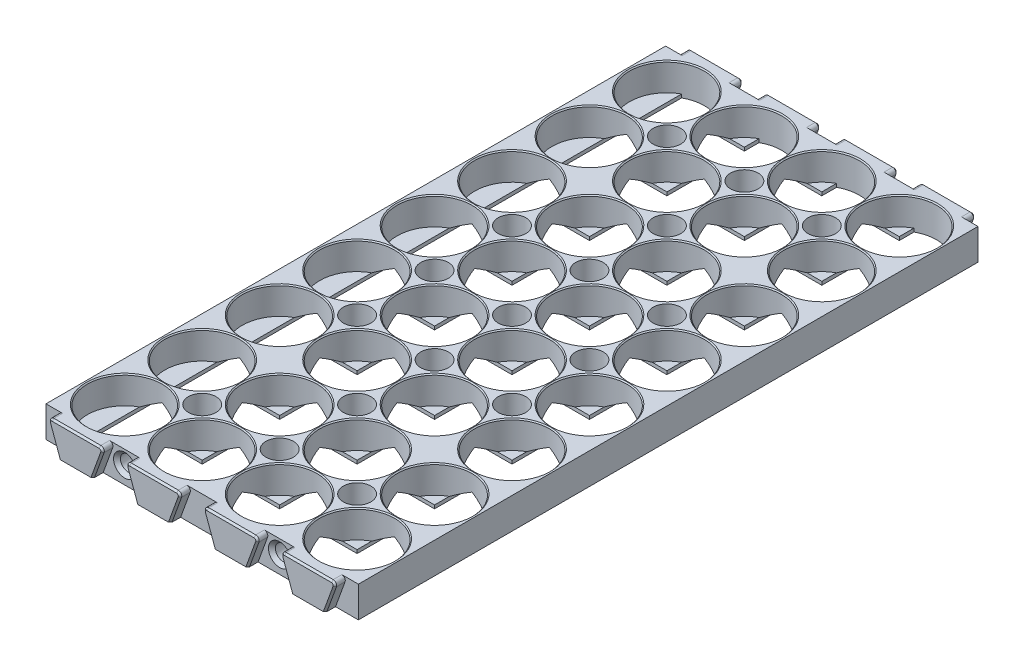
SolidWorks part; units mm, degrees
ref_plane "Front Plane" through (0, 0, 0) normal (0, 0, 1) x (1, 0, 0)
ref_plane "Top Plane" through (0, 0, 0) normal (0, 1, 0) x (1, 0, 0)
ref_plane "Right Plane" through (0, 0, 0) normal (1, 0, 0) x (0, 0, -1)
sketch "Sketch1" plane through (0, 0, 0) normal (0, 1, 0) x (1, 0, 0)
  line L0 (-11.25, 10.875) -> (11.25, 10.875) construction
  line L1 (-11.25, -11.25) -> (11.25, -11.25)
  line L2 (-11.25, -11.25) -> (-11.25, 11.25)
  line L3 (-11.25, 11.25) -> (11.25, 11.25)
  line L4 (11.25, -11.25) -> (11.25, 11.25)
  line L5 (-11.25, -11.25) -> (11.25, 11.25) construction
  line L6 (-11.25, 11.25) -> (11.25, -11.25) construction
  circle A0 centre (0, 0) radius 10.875
  point P0 (0, 0)
  dimension "D1" = 21.75
  dimension "D2" = 22.5
  dimension "D3" = 0.375
extrude "Boss-Extrude1" add sketch "Sketch1" along normal blind 8
sketch "Sketch2" plane through (0, 0, 0) normal (0, -1, 0) x (1, 0, 0)
  line L0 (5.25, 11.25) -> (-5.25, 11.25) construction
  line L1 (11.25, 11.25) -> (5.25, 11.25)
  line L2 (11.25, 11.25) -> (11.25, 5.25)
  line L3 (11.25, 5.25) -> (5.25, 5.25)
  line L4 (5.25, 11.25) -> (5.25, 5.25)
  line L5 (11.25, -11.25) -> (5.25, -11.25)
  line L6 (11.25, -11.25) -> (11.25, -5.25)
  line L7 (11.25, -5.25) -> (5.25, -5.25)
  line L8 (5.25, -11.25) -> (5.25, -5.25)
  line L9 (-11.25, -11.25) -> (-5.25, -11.25)
  line L10 (-11.25, -11.25) -> (-11.25, -5.25)
  line L11 (-11.25, -5.25) -> (-5.25, -5.25)
  line L12 (-5.25, -11.25) -> (-5.25, -5.25)
  line L13 (-11.25, 11.25) -> (-5.25, 11.25)
  line L14 (-11.25, 11.25) -> (-11.25, 5.25)
  line L15 (-11.25, 5.25) -> (-5.25, 5.25)
  line L16 (-5.25, 11.25) -> (-5.25, 5.25)
  line L17 (11.25, 5.25) -> (11.25, -5.25) construction
  line L18 (5.25, -11.25) -> (-5.25, -11.25) construction
  line L19 (-11.25, 5.25) -> (-11.25, -5.25) construction
  dimension "D1" = 10.5
extrude "Boss-Extrude2" add sketch "Sketch2" along normal blind 1
chamfer "Chamfer2" distance 0.3 angle 45 1 edges at (0, 8, 10.875)
pattern_linear "LPattern1" count 8 spacing 22.5 along (0, 0, 1) count 4 spacing 22.5 along (1, 0, 0) of "Boss-Extrude2", "Boss-Extrude1", "Chamfer2"
sketch "Sketch5" plane through (0, 0, -5.25) normal (0, 0, 1) x (1, 0, 0)
  line L0 (72.75, -1) -> (72.75, 0) construction
  line L20 (78.75, -1) -> (72.75, -1) construction
  line L25 (-5.25, -1) -> (-5.25, 0) construction
  line L26 (-5.25, -1) -> (-11.25, -1) construction
  line L27 (-11.25, -1) -> (-11.25, 0) construction
  line L29 (-5.25, 0) -> (-9.5238, 0) construction
  line L35 (-5.25, -1) -> (-5.25, 0)
  line L36 (-5.25, -1) -> (-11.25, -1)
  line L37 (-11.25, -1) -> (-11.25, 0)
  line L39 (-5.25, 0) -> (-11.25, 0)
  line L46 (78.75, -1) -> (78.75, 0) construction
  line L47 (78.75, 0) -> (77.0238, 0) construction
  line L48 (77.0238, 0) -> (72.75, 0) construction
  line L49 (72.75, -1) -> (72.75, 0)
  line L50 (78.75, -1) -> (72.75, -1)
  line L51 (78.75, -1) -> (78.75, 0)
  line L52 (78.75, 0) -> (77.0238, 0)
  line L53 (77.0238, 0) -> (72.75, 0)
  dimension "D1" = 6
extrude "Boss-Extrude3" add sketch "Sketch5" along normal up to surface (174 mm away)
sketch "Sketch6" plane through (0, 0, 0) normal (0, -1, 0) x (1, 0, 0)
  line L24 (62.25, -11.25) -> (72.75, -11.25) construction
  line L25 (72.75, -11.25) -> (72.75, -9.5238) construction
  line L26 (62.25, -9.5238) -> (62.25, -11.25) construction
  line L27 (39.75, -11.25) -> (50.25, -11.25) construction
  line L28 (50.25, -11.25) -> (50.25, -9.5238) construction
  line L29 (39.75, -9.5238) -> (39.75, -11.25) construction
  line L30 (17.25, -9.5238) -> (17.25, -11.25) construction
  line L31 (17.25, -11.25) -> (27.75, -11.25) construction
  line L32 (27.75, -11.25) -> (27.75, -9.5238) construction
  line L33 (-5.25, -9.5238) -> (-5.25, -11.25) construction
  line L34 (-5.25, -11.25) -> (5.25, -11.25) construction
  line L35 (5.25, -11.25) -> (5.25, -9.5238) construction
  line L48 (62.25, -11.25) -> (72.75, -11.25)
  line L49 (72.75, -11.25) -> (72.75, -9.5238)
  line L50 (62.25, -9.5238) -> (62.25, -11.25)
  line L51 (39.75, -11.25) -> (50.25, -11.25)
  line L52 (50.25, -11.25) -> (50.25, -9.5238)
  line L53 (39.75, -9.5238) -> (39.75, -11.25)
  line L54 (17.25, -9.5238) -> (17.25, -11.25)
  line L55 (17.25, -11.25) -> (27.75, -11.25)
  line L56 (27.75, -11.25) -> (27.75, -9.5238)
  line L57 (-5.25, -9.5238) -> (-5.25, -11.25)
  line L58 (-5.25, -11.25) -> (5.25, -11.25)
  line L59 (5.25, -11.25) -> (5.25, -9.5238)
  line L84 (5.25, 168.75) -> (-5.25, 168.75) construction
  line L85 (-5.25, 168.75) -> (-5.25, 167.0238) construction
  line L86 (5.25, 167.0238) -> (5.25, 168.75) construction
  line L87 (27.75, 167.0238) -> (27.75, 168.75) construction
  line L88 (27.75, 168.75) -> (17.25, 168.75) construction
  line L89 (17.25, 168.75) -> (17.25, 167.0238) construction
  line L90 (72.75, 167.0238) -> (72.75, 168.75) construction
  line L91 (72.75, 168.75) -> (62.25, 168.75) construction
  line L92 (62.25, 168.75) -> (62.25, 167.0238) construction
  line L93 (50.25, 167.0238) -> (50.25, 168.75) construction
  line L94 (50.25, 168.75) -> (39.75, 168.75) construction
  line L95 (39.75, 168.75) -> (39.75, 167.0238) construction
  line L96 (5.25, 168.75) -> (-5.25, 168.75)
  line L97 (-5.25, 168.75) -> (-5.25, 167.0238)
  line L98 (5.25, 167.0238) -> (5.25, 168.75)
  line L99 (27.75, 167.0238) -> (27.75, 168.75)
  line L100 (27.75, 168.75) -> (17.25, 168.75)
  line L101 (17.25, 168.75) -> (17.25, 167.0238)
  line L102 (72.75, 167.0238) -> (72.75, 168.75)
  line L103 (72.75, 168.75) -> (62.25, 168.75)
  line L104 (62.25, 168.75) -> (62.25, 167.0238)
  line L105 (50.25, 167.0238) -> (50.25, 168.75)
  line L106 (50.25, 168.75) -> (39.75, 168.75)
  line L107 (39.75, 168.75) -> (39.75, 167.0238)
  arc A8 (62.25, -9.5238) -> (72.75, -9.5238) centre (67.5, 0) ccw construction
  arc A9 (39.75, -9.5238) -> (50.25, -9.5238) centre (45, 0) ccw construction
  arc A10 (17.25, -9.5238) -> (27.75, -9.5238) centre (22.5, 0) ccw construction
  arc A11 (-5.25, -9.5238) -> (5.25, -9.5238) centre (0, 0) ccw construction
  arc A16 (62.25, -9.5238) -> (72.75, -9.5238) centre (67.5, 0) ccw
  arc A17 (39.75, -9.5238) -> (50.25, -9.5238) centre (45, 0) ccw
  arc A18 (17.25, -9.5238) -> (27.75, -9.5238) centre (22.5, 0) ccw
  arc A19 (-5.25, -9.5238) -> (5.25, -9.5238) centre (0, 0) ccw
  arc A28 (5.25, 167.0238) -> (-5.25, 167.0238) centre (0, 157.5) ccw construction
  arc A29 (27.75, 167.0238) -> (17.25, 167.0238) centre (22.5, 157.5) ccw construction
  arc A30 (72.75, 167.0238) -> (62.25, 167.0238) centre (67.5, 157.5) ccw construction
  arc A31 (50.25, 167.0238) -> (39.75, 167.0238) centre (45, 157.5) ccw construction
  arc A32 (5.25, 167.0238) -> (-5.25, 167.0238) centre (0, 157.5) ccw
  arc A33 (27.75, 167.0238) -> (17.25, 167.0238) centre (22.5, 157.5) ccw
  arc A34 (72.75, 167.0238) -> (62.25, 167.0238) centre (67.5, 157.5) ccw
  arc A35 (50.25, 167.0238) -> (39.75, 167.0238) centre (45, 157.5) ccw
extrude "Boss-Extrude4" add sketch "Sketch6" along normal up to surface (1 mm away) up to face at (-8.25, -1, 78.75)
sketch "Sketch7" plane through (0, 0, 0) normal (0, 0, 1) x (1, 0, 0)
  line L0 (-11.25, 8) -> (78.75, 8) construction
  line L1 (-5.25, 0) -> (5.25, 0)
  line L2 (-5.25, 0) -> (0, 5.25) construction
  line L3 (0, 5.25) -> (5.25, 0) construction
  line L4 (0, 0) -> (0, 8) construction
  line L6 (-5.25, 0) -> (0, 3.0311)
  line L7 (0, 3.0311) -> (5.25, 0)
  line L9 (-5.25, -1) -> (-5.25, 0) construction
  line L10 (5.25, -1) -> (5.25, 0) construction
  line L11 (-5.25, -1) -> (-5.25, 0) construction
  line L12 (5.25, -1) -> (5.25, 0) construction
  line L13 (17.25, 0) -> (22.5, 3.0311)
  line L14 (22.5, 3.0311) -> (27.75, 0)
  line L15 (17.25, 0) -> (27.75, 0)
  line L16 (39.75, 0) -> (45, 3.0311)
  line L17 (45, 3.0311) -> (50.25, 0)
  line L18 (39.75, 0) -> (50.25, 0)
  line L19 (62.25, 0) -> (67.5, 3.0311)
  line L20 (67.5, 3.0311) -> (72.75, 0)
  line L21 (62.25, 0) -> (72.75, 0)
  line L22 (-5.25, 0) -> (17.25, 0) construction
  dimension "D1" = 45
  dimension "D2" = 30
  dimension "D3" = 4.9689
  dimension "D5" = 22.5
  dimension "D4" = 4
extrude "Cut-Extrude1" cut sketch "Sketch7" along normal up to surface (162.75 mm away) up to face at (56.25, -0.3333, 162.75)
sketch "Sketch16" plane through (0, 0, 0) normal (1, 0, 0) x (0, 0, -1)
  line L2 (-5.25, -1) -> (-5.25, 0) construction
  line L3 (5.25, -1) -> (5.25, 0) construction
  line L4 (-5.25, 0) -> (0, 3.0311)
  line L5 (0, 3.0311) -> (5.25, 0)
  line L6 (-5.25, 0) -> (5.25, 0)
  line L7 (-5.25, -1) -> (-5.25, 0) construction
  line L8 (5.25, -1) -> (5.25, 0) construction
  line L9 (-22.5, 3.0311) -> (-17.25, 0)
  line L10 (-27.75, 0) -> (-17.25, 0)
  line L11 (-27.75, 0) -> (-22.5, 3.0311)
  line L12 (-45, 3.0311) -> (-39.75, 0)
  line L13 (-50.25, 0) -> (-39.75, 0)
  line L14 (-50.25, 0) -> (-45, 3.0311)
  line L15 (-67.5, 3.0311) -> (-62.25, 0)
  line L16 (-72.75, 0) -> (-62.25, 0)
  line L17 (-72.75, 0) -> (-67.5, 3.0311)
  line L18 (-90, 3.0311) -> (-84.75, 0)
  line L19 (-95.25, 0) -> (-84.75, 0)
  line L20 (-95.25, 0) -> (-90, 3.0311)
  line L21 (-112.5, 3.0311) -> (-107.25, 0)
  line L22 (-117.75, 0) -> (-107.25, 0)
  line L23 (-117.75, 0) -> (-112.5, 3.0311)
  line L24 (-135, 3.0311) -> (-129.75, 0)
  line L25 (-140.25, 0) -> (-129.75, 0)
  line L26 (-140.25, 0) -> (-135, 3.0311)
  line L27 (-157.5, 3.0311) -> (-152.25, 0)
  line L28 (-162.75, 0) -> (-152.25, 0)
  line L29 (-162.75, 0) -> (-157.5, 3.0311)
  line L30 (-180, 3.0311) -> (-174.75, 0)
  line L31 (-185.25, 0) -> (-174.75, 0)
  line L32 (-185.25, 0) -> (-180, 3.0311)
  line L33 (-202.5, 3.0311) -> (-197.25, 0)
  line L34 (-207.75, 0) -> (-197.25, 0)
  line L35 (-207.75, 0) -> (-202.5, 3.0311)
  line L36 (-225, 3.0311) -> (-219.75, 0)
  line L37 (-230.25, 0) -> (-219.75, 0)
  line L38 (-230.25, 0) -> (-225, 3.0311)
  line L39 (-247.5, 3.0311) -> (-242.25, 0)
  line L40 (-252.75, 0) -> (-242.25, 0)
  line L41 (-252.75, 0) -> (-247.5, 3.0311)
  line L42 (0, 3.0311) -> (-22.5, 3.0311) construction
  dimension "D1" = 30
  dimension "D3" = 22.5
  dimension "D2" = 12
extrude "Cut-Extrude7" cut sketch "Sketch16" along normal up to surface (62.25 mm away) up to face at (62.25, -0.3333, 11.25)
sketch "Sketch8" plane through (0, 0, -11.25) normal (0, 0, -1) x (-1, 0, 0)
  line L0 (0, -1) -> (0, 8) construction
  line L1 (-27.4743, -1) -> (-30.75, 8)
  line L2 (-78.75, 8) -> (11.25, 8) construction
  line L3 (4.9743, -1) -> (-4.9743, -1)
  line L4 (-4.9743, -1) -> (-8.25, 8)
  line L5 (-8.25, 8) -> (8.25, 8)
  line L6 (4.9743, -1) -> (8.25, 8)
  line L7 (11.25, 8) -> (11.25, -1) construction
  line L8 (11.25, -1) -> (-78.75, -1) construction
  line L9 (-30.75, 8) -> (-14.25, 8)
  line L10 (-78.75, 8) -> (11.25, 8) construction
  line L11 (-17.5257, -1) -> (-14.25, 8)
  line L12 (-17.5257, -1) -> (-27.4743, -1)
  line L13 (-49.9743, -1) -> (-53.25, 8)
  line L14 (-53.25, 8) -> (-36.75, 8)
  line L15 (-40.0257, -1) -> (-36.75, 8)
  line L16 (-40.0257, -1) -> (-49.9743, -1)
  line L17 (-72.4743, -1) -> (-75.75, 8)
  line L18 (-75.75, 8) -> (-59.25, 8)
  line L19 (-62.5257, -1) -> (-59.25, 8)
  line L20 (-62.5257, -1) -> (-72.4743, -1)
  line L21 (-4.9743, -1) -> (-27.4743, -1) construction
  line L22 (-78.75, 8) -> (11.25, 8) construction
  dimension "D1" = 70
  dimension "D2" = 3
  dimension "D4" = 22.5
  dimension "D5" = 9
  dimension "D3" = 4
sketch "Sketch9" plane through (0, 0, 168.75) normal (0, 0, 1) x (1, 0, 0)
  line L24 (-4.9743, -1) -> (4.9743, -1)
  line L25 (4.9743, -1) -> (8.25, 8)
  line L26 (8.25, 8) -> (-8.25, 8)
  line L27 (-8.25, 8) -> (-4.9743, -1)
  line L28 (-4.9743, -1) -> (4.9743, -1)
  line L29 (4.9743, -1) -> (8.25, 8)
  line L30 (8.25, 8) -> (-8.25, 8)
  line L31 (-8.25, 8) -> (-4.9743, -1)
  line L32 (72.4743, -1) -> (75.75, 8)
  line L33 (75.75, 8) -> (59.25, 8)
  line L34 (59.25, 8) -> (62.5257, -1)
  line L35 (62.5257, -1) -> (72.4743, -1)
  line L36 (72.4743, -1) -> (75.75, 8)
  line L37 (75.75, 8) -> (59.25, 8)
  line L38 (59.25, 8) -> (62.5257, -1)
  line L39 (62.5257, -1) -> (72.4743, -1)
  line L40 (49.9743, -1) -> (53.25, 8)
  line L41 (53.25, 8) -> (36.75, 8)
  line L42 (36.75, 8) -> (40.0257, -1)
  line L43 (40.0257, -1) -> (49.9743, -1)
  line L44 (49.9743, -1) -> (53.25, 8)
  line L45 (53.25, 8) -> (36.75, 8)
  line L46 (36.75, 8) -> (40.0257, -1)
  line L47 (40.0257, -1) -> (49.9743, -1)
  line L48 (14.25, 8) -> (17.5257, -1)
  line L49 (17.5257, -1) -> (27.4743, -1)
  line L50 (27.4743, -1) -> (30.75, 8)
  line L51 (30.75, 8) -> (14.25, 8)
  line L52 (14.25, 8) -> (17.5257, -1)
  line L53 (17.5257, -1) -> (27.4743, -1)
  line L54 (27.4743, -1) -> (30.75, 8)
  line L55 (30.75, 8) -> (14.25, 8)
  dimension "D1" = 0
  dimension "D2" = 0
  dimension "D3" = 0
  dimension "D4" = 0
extrude "Boss-Extrude5" add sketch "Sketch8" along normal blind 3
extrude "Boss-Extrude6" add sketch "Sketch9" along normal blind 3
fillet "Fillet1" radius 1 16 edges at (14.25, 8, -12.75) (8.25, 8, -12.75) (-8.25, 8, -12.75) (30.75, 8, -12.75) (59.25, 8, -12.75) (53.25, 8, -12.75) (36.75, 8, -12.75) (75.75, 8, -12.75) (-8.25, 8, 170.25) (8.25, 8, 170.25) (14.25, 8, 170.25) (30.75, 8, 170.25) (36.75, 8, 170.25) (53.25, 8, 170.25) (59.25, 8, 170.25) (75.75, 8, 170.25)
chamfer "Chamfer3" distance 0.5 angle 45 40 edges at (6.3679, 2.829, -14.25) (0, 8, -14.25) (-6.3679, 2.829, -14.25) (73.8679, 2.829, -14.25) (67.5, 8, -14.25) (61.1321, 2.829, -14.25) (51.3679, 2.829, -14.25) (45, 8, -14.25) (38.6321, 2.829, -14.25) (28.8679, 2.829, -14.25) (22.5, 8, -14.25) (16.1321, 2.829, -14.25) (73.8679, 2.829, 171.75) (61.1321, 2.829, 171.75) (67.5, 8, 171.75) (51.3679, 2.829, 171.75) (38.6321, 2.829, 171.75) (45, 8, 171.75) (28.8679, 2.829, 171.75) (16.1321, 2.829, 171.75) (22.5, 8, 171.75) (6.3679, 2.829, 171.75) (-6.3679, 2.829, 171.75) (0, 8, 171.75) (75.141, 7.5736, 171.75) (59.859, 7.5736, 171.75) (52.641, 7.5736, 171.75) (37.359, 7.5736, 171.75) (30.141, 7.5736, 171.75) (14.859, 7.5736, 171.75) (7.641, 7.5736, 171.75) (-7.641, 7.5736, 171.75) (75.141, 7.5736, -14.25) (59.859, 7.5736, -14.25) (52.641, 7.5736, -14.25) (37.359, 7.5736, -14.25) (30.141, 7.5736, -14.25) (14.859, 7.5736, -14.25) (7.641, 7.5736, -14.25) (-7.641, 7.5736, -14.25)
sketch "Sketch10" plane through (0, 0, -11.25) normal (0, 0, -1) x (-1, 0, 0)
  line L0 (-11.25, -1) -> (-11.25, 8) construction
  line L2 (-4.9743, -1) -> (-17.5257, -1) construction
  line L4 (-14.25, 8) -> (-8.25, 8) construction
  line L5 (-33.75, 8) -> (-33.75, -1) construction
  line L6 (-36.75, 8) -> (-30.75, 8) construction
  line L7 (-27.4743, -1) -> (-40.0257, -1) construction
  circle A0 centre (-11.25, 4) radius 2.25
  circle A1 centre (-56.25, 4) radius 2.25
  dimension "D2" = 4.5
  dimension "D1" = 4
sketch "Sketch11" plane through (0, 0, 168.75) normal (0, 0, 1) x (1, 0, 0)
  circle A0 centre (11.25, 4) radius 2.25 construction
  circle A1 centre (11.25, 4) radius 2.25
  circle A2 centre (56.25, 4) radius 2.25 construction
  circle A3 centre (56.25, 4) radius 2.25
extrude "Cut-Extrude2" cut sketch "Sketch10" against normal blind 5
extrude "Cut-Extrude3" cut sketch "Sketch11" against normal blind 5
chamfer "Chamfer5" distance 1 angle 45 4 edges at (58.5, 4, -11.25) (9, 4, -11.25) (13.5, 4, 168.75) (58.5, 4, 168.75)
sketch "Sketch17" plane through (0, -1, 0) normal (0, -1, 0) x (1, 0, 0)
  line L0 (5.25, 5.25) -> (17.25, 17.25) construction
  line L1 (11.25, 11.25) -> (33.75, 11.25) construction
  circle A0 centre (11.25, 11.25) radius 4
  circle A1 centre (33.75, 11.25) radius 4
  circle A2 centre (56.25, 11.25) radius 4
  circle A33 centre (33.75, 146.25) radius 4 [skipped]
  circle A34 centre (56.25, 146.25) radius 4 [skipped]
  circle A35 centre (33.75, 168.75) radius 4 [skipped]
  circle A36 centre (33.75, 191.25) radius 4 [skipped]
  circle A37 centre (56.25, 191.25) radius 4 [skipped]
  circle A38 centre (33.75, 213.75) radius 4 [skipped]
  circle A39 centre (56.25, 213.75) radius 4 [skipped]
  circle A40 centre (33.75, 236.25) radius 4 [skipped]
  circle A41 centre (56.25, 236.25) radius 4 [skipped]
  circle A42 centre (11.25, 146.25) radius 4 [skipped]
  circle A43 centre (11.25, 191.25) radius 4 [skipped]
  circle A44 centre (11.25, 213.75) radius 4 [skipped]
  circle A45 centre (11.25, 236.25) radius 4 [skipped]
  circle A46 centre (56.25, 168.75) radius 4 construction
  circle A47 centre (11.25, 168.75) radius 4 construction
  circle A48 centre (33.75, 123.75) radius 4 [skipped]
  circle A49 centre (56.25, 123.75) radius 4 [skipped]
  circle A50 centre (11.25, 123.75) radius 4 [skipped]
  circle A51 centre (11.25, 258.75) radius 4
  circle A52 centre (33.75, 258.75) radius 4
  circle A53 centre (56.25, 258.75) radius 4
  circle A54 centre (11.25, 281.25) radius 4
  circle A55 centre (33.75, 281.25) radius 4
  circle A56 centre (56.25, 281.25) radius 4
  circle A57 centre (33.75, 33.75) radius 4 [skipped]
  circle A58 centre (33.75, 56.25) radius 4 [skipped]
  circle A59 centre (56.25, 56.25) radius 4 [skipped]
  circle A60 centre (33.75, 78.75) radius 4 [skipped]
  circle A61 centre (56.25, 78.75) radius 4 [skipped]
  circle A62 centre (33.75, 101.25) radius 4 [skipped]
  circle A63 centre (56.25, 101.25) radius 4 [skipped]
  circle A64 centre (11.25, 56.25) radius 4 [skipped]
  circle A65 centre (11.25, 78.75) radius 4 [skipped]
  circle A66 centre (11.25, 101.25) radius 4 [skipped]
  circle A67 centre (56.25, 33.75) radius 4 construction
  circle A68 centre (11.25, 33.75) radius 4 construction
  circle A69 centre (11.25, 33.75) radius 4 construction
  circle A70 centre (33.75, 33.75) radius 4
  circle A71 centre (56.25, 33.75) radius 4 construction
  circle A72 centre (11.25, 56.25) radius 4
  circle A73 centre (33.75, 56.25) radius 4
  circle A74 centre (56.25, 56.25) radius 4
  circle A75 centre (11.25, 78.75) radius 4
  circle A76 centre (33.75, 78.75) radius 4
  circle A77 centre (56.25, 78.75) radius 4
  circle A78 centre (11.25, 101.25) radius 4
  circle A79 centre (33.75, 101.25) radius 4
  circle A80 centre (56.25, 101.25) radius 4
  circle A81 centre (11.25, 123.75) radius 4 construction
  circle A82 centre (33.75, 123.75) radius 4
  circle A83 centre (56.25, 123.75) radius 4 construction
  circle A84 centre (11.25, 146.25) radius 4
  circle A85 centre (33.75, 146.25) radius 4
  circle A86 centre (56.25, 146.25) radius 4
  dimension "D4" = 22.5
  dimension "D1" = 8
  dimension "D3" = 13
  dimension "D5" = 7
extrude "Cut-Extrude8" cut sketch "Sketch17" against normal through all
sketch "Sketch18" plane through (0, -1, 0) normal (0, -1, 0) x (1, 0, 0)
  line L0 (50.25, 117.75) -> (62.25, 117.75) construction
  line L1 (50.25, 129.75) -> (50.25, 117.75) construction
  line L2 (5.25, 117.75) -> (17.25, 129.75) construction
  line L3 (5.25, 27.75) -> (17.25, 39.75) construction
  line L4 (50.25, 27.75) -> (62.25, 39.75) construction
  line L38 (78.75, 78.75) -> (-11.25, 78.75) construction
  line L39 (78.75, -11.25) -> (78.75, 168.75) construction
  line L40 (-11.25, 168.75) -> (-11.25, -11.25) construction
  line L42 (50.25, 117.75) -> (62.25, 129.75) construction
  circle A0 centre (11.25, 33.75) radius 2.1
  circle A4 centre (56.25, 33.75) radius 2.1
  circle A7 centre (56.25, 123.75) radius 2.1
  circle A8 centre (11.25, 123.75) radius 2.1
  dimension "D1" = 4.2
extrude "Cut-Extrude9" cut sketch "Sketch18" against normal blind 4
sketch "Sketch19" plane through (0, -1, 0) normal (0, -1, 0) x (1, 0, 0)
  line L0 (78.75, 78.75) -> (-11.25, 78.75) construction
  line L1 (78.75, -11.25) -> (78.75, 168.75) construction
  line L2 (-11.25, 168.75) -> (-11.25, -11.25) construction
  circle A2 centre (56.25, 123.75) radius 1.7
  circle A3 centre (11.25, 33.75) radius 1.7
  circle A4 centre (11.25, 123.75) radius 1.7
  circle A5 centre (56.25, 33.75) radius 1.7
  dimension "D1" = 3.4
extrude "Cut-Extrude10" cut sketch "Sketch19" against normal offset from surface (7 mm away) 2 up to face at (11.25, 8, 97.25)
chamfer "Chamfer6" distance 1 angle 45 4 edges at (11.25, -1, 121.65) (56.25, -1, 121.65) (56.25, -1, 31.65) (11.25, -1, 31.65)
sketch "Sketch22" plane through (0, 8, 0) normal (0, 1, 0) x (1, 0, 0)
  line L0 (-11.25, -168.75) -> (-6.8219, -168.75) construction
  line L1 (-11.25, 11.25) -> (-11.625, 11.25)
  line L2 (-11.25, 11.25) -> (-11.25, -168.75)
  line L3 (-11.25, -168.75) -> (-11.625, -168.75)
  line L4 (-11.625, 11.25) -> (-11.625, -168.75)
  line L5 (33.75, 11.25) -> (33.75, -168.75) construction
  line L6 (36.75, 11.25) -> (30.75, 11.25) construction
  line L7 (30.75, -168.75) -> (36.75, -168.75) construction
  line L14 (79.125, 11.25) -> (79.125, -168.75)
  line L15 (78.75, -168.75) -> (79.125, -168.75)
  line L16 (78.75, 11.25) -> (78.75, -168.75)
  line L17 (78.75, 11.25) -> (79.125, 11.25)
  arc A1 (-5.25, 9.5238) -> (-5.25, -9.5238) centre (0, 0) ccw construction
  point P10 (-10.875, 0)
  dimension "D1" = 0.75
  dimension "D2" = 0.375
extrude "Boss-Extrude7" add sketch "Sketch22" against normal up to surface (9 mm away) up to face at (33.75, -1, 78.75)
sketch "Sketch14" plane through (0, -1, 0) normal (0, -1, 0) x (1, 0, 0)
  line L0 (-10.25, 76.2941) -> (-10.25, 81.2059)
  line L2 (-6.25, 77.75) -> (-6.25, 79.75)
  line L4 (-11.625, -11.25) -> (-11.625, 168.75) construction
  line L19 (-5.25, 11.25) -> (-11.625, 11.25) construction
  line L30 (-5.25, 9.5238) -> (-5.25, 12.9762) construction
  line L39 (-6.25, 10.25) -> (-6.25, 12.25)
  line L51 (-10.25, 8.7941) -> (-10.25, 13.7059)
  line L52 (-10.25, 13.7059) -> (-6.25, 12.25)
  line L53 (33.75, -11.25) -> (33.75, 168.75) construction
  line L54 (27.4743, -11.25) -> (40.0257, -11.25) construction
  line L55 (40.0257, 168.75) -> (27.4743, 168.75) construction
  line L56 (-5.25, 146.25) -> (-11.625, 146.25) construction
  line L58 (-5.25, -9.5238) -> (-5.25, 167.0238) construction
  line L59 (-10.25, 81.2059) -> (-6.25, 79.75)
  line L60 (-5.25, 78.75) -> (-11.625, 78.75) construction
  line L61 (-10.25, 148.7059) -> (-6.25, 147.25)
  line L64 (-10.25, 143.7941) -> (-6.25, 145.25)
  line L65 (-10.25, 148.7059) -> (-10.25, 143.7941)
  line L66 (-6.25, 147.25) -> (-6.25, 145.25)
  line L67 (72.75, 78.75) -> (79.125, 78.75) construction
  line L69 (72.75, 146.25) -> (79.125, 146.25) construction
  line L70 (72.75, 11.25) -> (79.125, 11.25) construction
  line L71 (77.75, 76.2941) -> (73.75, 77.75)
  line L75 (-10.25, 8.7941) -> (-6.25, 10.25)
  line L76 (77.75, 8.7941) -> (73.75, 10.25)
  line L77 (73.75, 147.25) -> (73.75, 145.25)
  line L78 (77.75, 148.7059) -> (77.75, 143.7941)
  line L79 (77.75, 143.7941) -> (73.75, 145.25)
  line L84 (77.75, 148.7059) -> (73.75, 147.25)
  line L85 (77.75, 81.2059) -> (73.75, 79.75)
  line L86 (77.75, 13.7059) -> (73.75, 12.25)
  line L87 (77.75, 8.7941) -> (77.75, 13.7059)
  line L95 (-10.25, 76.2941) -> (-6.25, 77.75)
  line L96 (73.75, 10.25) -> (73.75, 12.25)
  line L97 (73.75, 77.75) -> (73.75, 79.75)
  line L98 (77.75, 76.2941) -> (77.75, 81.2059)
  point P0 (-10.25, 146.25)
  point P2 (-10.25, 78.75)
  point P8 (-6.25, 11.25)
  point P11 (-10.25, 11.25)
  point P31 (-6.25, 78.75)
  point P32 (-6.25, 146.25)
  point P54 (73.75, 146.25)
  point P55 (73.75, 78.75)
  point P56 (77.75, 11.25)
  point P57 (73.75, 11.25)
  point P58 (77.75, 78.75)
  point P59 (77.75, 146.25)
  dimension "D1" = 70
  dimension "D2" = 1
  dimension "D3" = 1.375
  dimension "D4" = 4
  dimension "D5" = 70
  dimension "D7" = 4
  dimension "D8" = 1
extrude "Cut-Extrude11" cut sketch "Sketch14" against normal blind 2
chamfer "Chamfer7" distance 0.5 angle 45 24 edges at (-10.25, -1, 146.25) (-8.25, -1, 144.5221) (-6.25, -1, 146.25) (-8.25, -1, 147.9779) (73.75, -1, 146.25) (75.75, -1, 144.5221) (77.75, -1, 146.25) (75.75, -1, 147.9779) (-8.25, -1, 77.0221) (-6.25, -1, 78.75) (-10.25, -1, 78.75) (-8.25, -1, 80.4779) (77.75, -1, 78.75) (75.75, -1, 77.0221) (73.75, -1, 78.75) (75.75, -1, 80.4779) (77.75, -1, 11.25) (75.75, -1, 9.5221) (73.75, -1, 11.25) (75.75, -1, 12.9779) (-6.25, -1, 11.25) (-8.25, -1, 9.5221) (-10.25, -1, 11.25) (-8.25, -1, 12.9779)
equation "\"cell_side\"= 22.50"
equation "\"D2@Sketch1\"=\"cell_side\""
equation "\"D5@Sketch7\"=\"cell_side\""
equation "\"D3@Sketch16\"=\"cell_side\""
equation "\"D4@Sketch8\"=\"cell_side\""
equation "\"D3@LPattern1\"=\"cell_side\""
equation "\"D4@LPattern1\"=\"cell_side\""
equation "\"D4@Sketch17\"=\"cell_side\""
